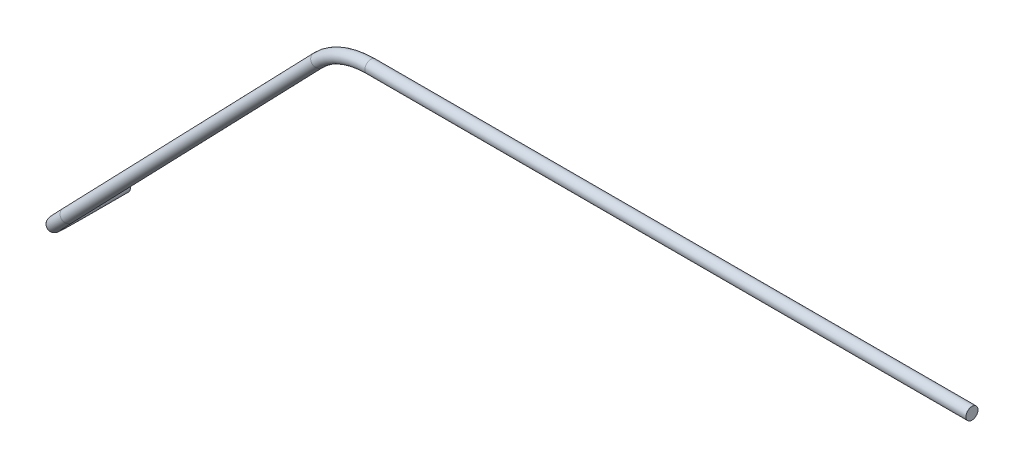
SolidWorks part; units mm, degrees
material "3003 Alloy"
ref_plane "Front Plane" through (0, 0, 0) normal (0, 0, 1) x (1, 0, 0)
ref_plane "Top Plane" through (0, 0, 0) normal (0, 1, 0) x (1, 0, 0)
ref_plane "Right Plane" through (0, 0, 0) normal (1, 0, 0) x (0, 0, -1)
sketch "Sketch1" plane through (0, 0, 0) normal (0, 0, 1) x (1, 0, 0)
  circle A2 centre (0, 25.4) radius 4.7625
sketch3d "3DSketch1"
  line L0 (0, 25.4, 0) -> (0, 25.4, 23.8192)
  line L1 (38.9866, 65.683, 83.6896) -> (257.4796, 291.4411, 104.3675)
  line L2 (300.681, 309.7276, 106.0424) -> (775.1776, 309.7276, 106.0424)
  arc A0 (0, 25.4, 23.8192) -> (38.9866, 65.683, 83.6896) centre (41.727, 68.5145, 23.8192) ccw
  arc A1 (257.4796, 291.4411, 104.3675) -> (300.681, 309.7276, 106.0424) centre (300.681, 249.9777, 100.5698) ccw
  point P7 (0, 25.4, 80)
  point P8 (-1.3875, 110.2415, 23.8192)
  point P11 (275.1776, 309.7276, 106.0424)
  point P12 (300.681, 255.4504, 40.8199)
  dimension "D3" = 60
  dimension "D1" = 80
  dimension "D2" = 500
sweep "Sweep1" add profiles "Sketch1" path "3DSketch1"
